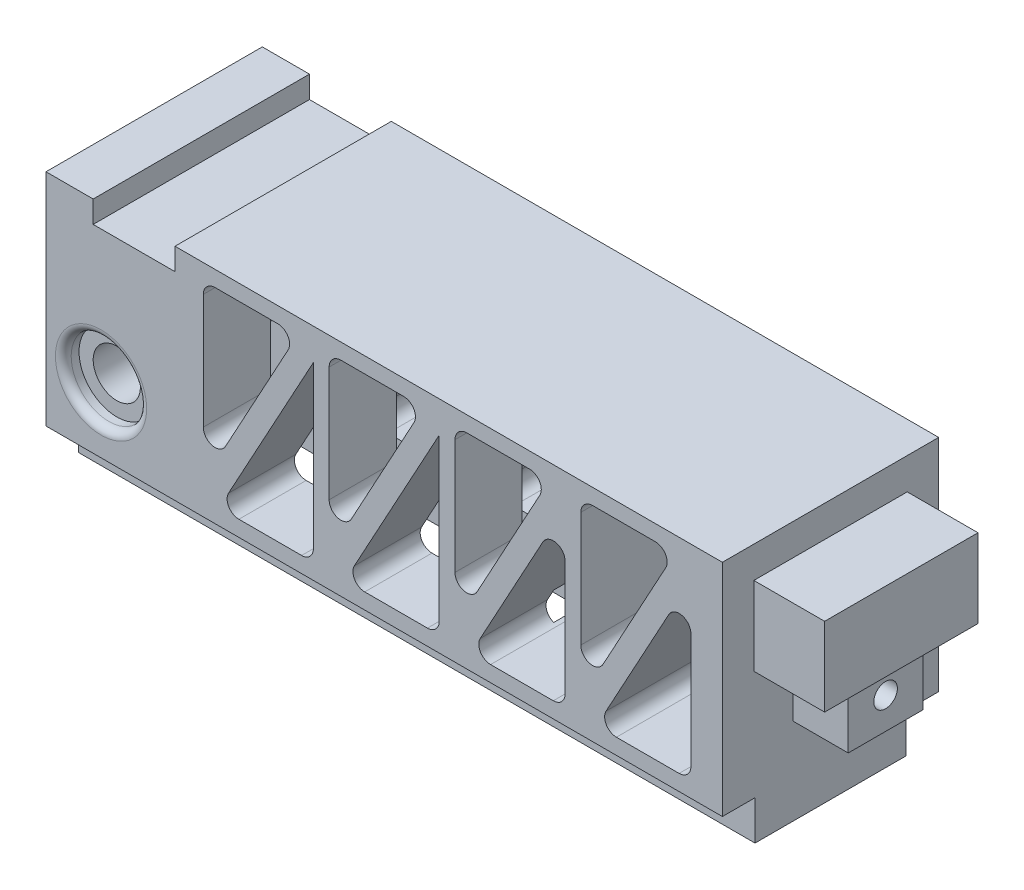
SolidWorks part; units mm, degrees
ref_plane "Front Plane" through (0, 0, 0) normal (0, 0, 1) x (1, 0, 0)
ref_plane "Top Plane" through (0, 0, 0) normal (0, 1, 0) x (1, 0, 0)
ref_plane "Right Plane" through (0, 0, 0) normal (1, 0, 0) x (0, 0, -1)
sketch "Sketch2" plane through (0, 0, 0) normal (0, 1, 0) x (1, 0, 0)
  line L1 (0, 0) -> (86, 0)
  line L2 (0, 0) -> (0, 4.4)
  line L3 (0, 4.4) -> (56, 4.4)
  line L4 (86, 0) -> (86, 4.15)
  line L5 (0, 14.8) -> (56, 14.8)
  line L6 (0, 14.8) -> (0, 19.2)
  line L7 (0, 19.2) -> (86, 19.2)
  line L8 (86, 14.25) -> (86, 19.2)
  line L10 (86, 14.25) -> (86, 4.15)
  line L12 (56, 14.8) -> (56, 4.4)
  dimension "D1" = 4.4
  dimension "D2" = 10.4
  dimension "D3" = 19.2
  dimension "D4" = 86
  dimension "D5" = 86
  dimension "D6" = 30
extrude "Boss-Extrude2" add sketch "Sketch2" against normal blind 5
sketch "Sketch3" plane through (0, 0, 0) normal (0, 1, 0) x (1, 0, 0)
  line L6 (86, 19.2) -> (0, 19.2) construction
  line L7 (0, 14.8) -> (56, 14.8)
  line L8 (0, 14.8) -> (0, 23.35)
  line L9 (0, 23.35) -> (56, 23.35)
  line L10 (56, 14.8) -> (56, 23.35)
  line L11 (0, 4.4) -> (56, 4.4)
  line L12 (0, 4.4) -> (0, -4.15)
  line L13 (0, -4.15) -> (56, -4.15)
  line L14 (56, 4.4) -> (56, -4.15)
  line L15 (0, 0) -> (86, 0) construction
  dimension "D1" = 56
  dimension "D2" = 56
  dimension "D3" = 4.15
  dimension "D4" = 4.15
extrude "Boss-Extrude3" add sketch "Sketch3" along normal blind 28
sketch "Sketch4" plane through (0, 0, 4.15) normal (0, 0, 1) x (1, 0, 0)
  line L0 (0, 0) -> (56, 0) construction
  line L1 (0, 28) -> (0, 0) construction
  circle A0 centre (7, 8.3) radius 3
  dimension "D1" = 6
  dimension "D2" = 8.3
  dimension "D3" = 7
extrude "Cut-Extrude1" cut sketch "Sketch4" against normal through all both and the other way through all
sketch "Sketch5" plane through (0, 0, 4.15) normal (0, 0, 1) x (1, 0, 0)
  circle A0 centre (7, 8.3) radius 4.8
  dimension "D1" = 9.6
extrude "Cut-Extrude2" cut sketch "Sketch5" against normal blind 2 and the other way through all
sketch "Sketch6" plane through (0, 0, -23.35) normal (0, 0, -1) x (-1, 0, 0)
  circle A0 centre (-7, 8.3) radius 4.8
  dimension "D1" = 9.6
extrude "Cut-Extrude3" cut sketch "Sketch6" against normal blind 3.2
sketch "Sketch7" plane through (0, 28, 0) normal (0, 1, 0) x (1, 0, 0)
  line L1 (0, 14.8) -> (56, 14.8)
  line L2 (0, 14.8) -> (0, 4.4)
  line L3 (0, 4.4) -> (56, 4.4)
  line L4 (56, 14.8) -> (56, 4.4)
extrude "Boss-Extrude4" add sketch "Sketch7" against normal blind 5
sketch "Sketch8" plane through (0, 0, 0) normal (0, 1, 0) x (1, 0, 0)
  line L1 (56, -4.15) -> (86, -4.15)
  line L2 (56, -4.15) -> (56, 23.35)
  line L3 (56, 23.35) -> (86, 23.35)
  line L4 (86, -4.15) -> (86, 23.35)
  dimension "D1" = 27.5
  dimension "D2" = 30
extrude "Boss-Extrude5" add sketch "Sketch8" along normal blind 28
sketch "Sketch12" plane through (0, 0, 4.15) normal (0, 0, 1) x (1, 0, 0)
  line L0 (82, 24) -> (82, 2)
  line L1 (82, 2) -> (70, 2)
  line L2 (70, 2) -> (82, 24)
  line L3 (0, 0) -> (86, 0) construction
  line L4 (86, 28) -> (86, 0) construction
  line L5 (0, 28) -> (86, 28) construction
  line L6 (80, 26) -> (68, 26)
  line L7 (68, 26) -> (68, 4)
  line L8 (68, 4) -> (80, 26)
  line L9 (0, 0) -> (86, 0) construction
  dimension "D1" = 2
  dimension "D2" = 4
  dimension "D3" = 4
  dimension "D4" = 12
  dimension "D5" = 2
  dimension "D6" = 4
  dimension "D7" = 12
  dimension "D8" = 14
extrude "Cut-Extrude4" cut sketch "Sketch12" against normal through all both and the other way through all
pattern_linear "LPattern1" count 4 spacing 16 along (-1, 0, 0) of "Cut-Extrude4"
sketch "Sketch11" plane through (0, 26, 0) normal (0, -1, 0) x (1, 0, 0)
  line L1 (0, -14.8) -> (56, -14.8) construction
  line L2 (56, -14.8) -> (56, -4.4) construction
  circle A0 centre (29.4, -9.55) radius 1.5
  dimension "D1" = 3
  dimension "D2" = 5.25
  dimension "D3" = 26.6
extrude "Boss-Extrude6" add sketch "Sketch11" along normal blind 7
fillet "Fillet1" radius 1.5 28 edges at (82, 24, -9.6) (66, 24, -9.6) (66, 2, -9.6) (36, 26, -9.6) (20, 26, -9.6) (20, 4, -19.075) (22, 2, -19.075) (22, 2, -0.125) (20, 4, -0.125) (34, 2, -19.075) (34, 2, -0.125) (36, 4, -0.125) (36, 4, -19.075) (48, 26, -9.6) (38, 2, -19.075) (38, 2, -0.125) (50, 2, -0.125) (52, 26, -9.6) (52, 4, -19.075) (52, 4, -0.125) (54, 2, -0.125) (64, 26, -9.6) (68, 4, -9.6) (68, 26, -9.6) (80, 26, -9.6) (82, 2, -9.6) (70, 2, -9.6) (32, 26, -9.6)
sketch "Sketch13" plane through (86, 0, 0) normal (1, 0, 0) x (0, 0, -1)
  line L0 (-4.15, 28) -> (-4.15, 0) construction
  line L1 (-0.15, 24) -> (19.35, 24)
  line L2 (-0.15, 24) -> (-0.15, 14)
  line L3 (-0.15, 14) -> (19.35, 14)
  line L4 (19.35, 24) -> (19.35, 14)
  line L5 (23.35, 28) -> (23.35, 0) construction
  line L6 (-4.15, 28) -> (23.35, 28) construction
  dimension "D1" = 4
  dimension "D2" = 4
  dimension "D3" = 4
  dimension "D4" = 10
extrude "Boss-Extrude7" add sketch "Sketch13" along normal blind 9
sketch "Sketch14" plane through (86, 0, 0) normal (1, 0, 0) x (0, 0, -1)
  line L0 (-0.15, 14) -> (19.35, 14) construction
  line L1 (4.85, 14) -> (14.35, 14)
  line L2 (4.85, 14) -> (4.85, 6)
  line L3 (4.85, 6) -> (14.35, 6)
  line L4 (14.35, 14) -> (14.35, 6)
  line L5 (-0.15, 24) -> (-0.15, 14) construction
  line L6 (19.35, 14) -> (19.35, 24) construction
  dimension "D1" = 5
  dimension "D2" = 5
  dimension "D3" = 8
extrude "Boss-Extrude8" add sketch "Sketch14" along normal blind 7
sketch "Sketch15" plane through (93, 0, 0) normal (1, 0, 0) x (0, 0, -1)
  line L0 (14.35, 6) -> (14.35, 14) construction
  line L2 (4.85, 6) -> (14.35, 6) construction
  circle A0 centre (9.6, 10) radius 1.5
  dimension "D1" = 4.75
  dimension "D2" = 4
  dimension "D3" = 3
extrude "Cut-Extrude5" cut sketch "Sketch15" against normal blind 5
sketch "Sketch16" plane through (0, 28, 0) normal (0, 1, 0) x (1, 0, 0)
  line L0 (86, 23.35) -> (0, 23.35) construction
  line L1 (6, 23.35) -> (16.4, 23.35)
  line L2 (6, 23.35) -> (6, -4.15)
  line L3 (6, -4.15) -> (16.4, -4.15)
  line L4 (16.4, 23.35) -> (16.4, -4.15)
  line L5 (0, -4.15) -> (86, -4.15) construction
  line L6 (0, 23.35) -> (0, -4.15) construction
  dimension "D1" = 10.4
  dimension "D2" = 6
extrude "Cut-Extrude6" cut sketch "Sketch16" against normal blind 2.8
fillet "Fillet2" radius 1 2 edges at (2.2, 8.3, 4.15) (2.2, 8.3, -23.35)
